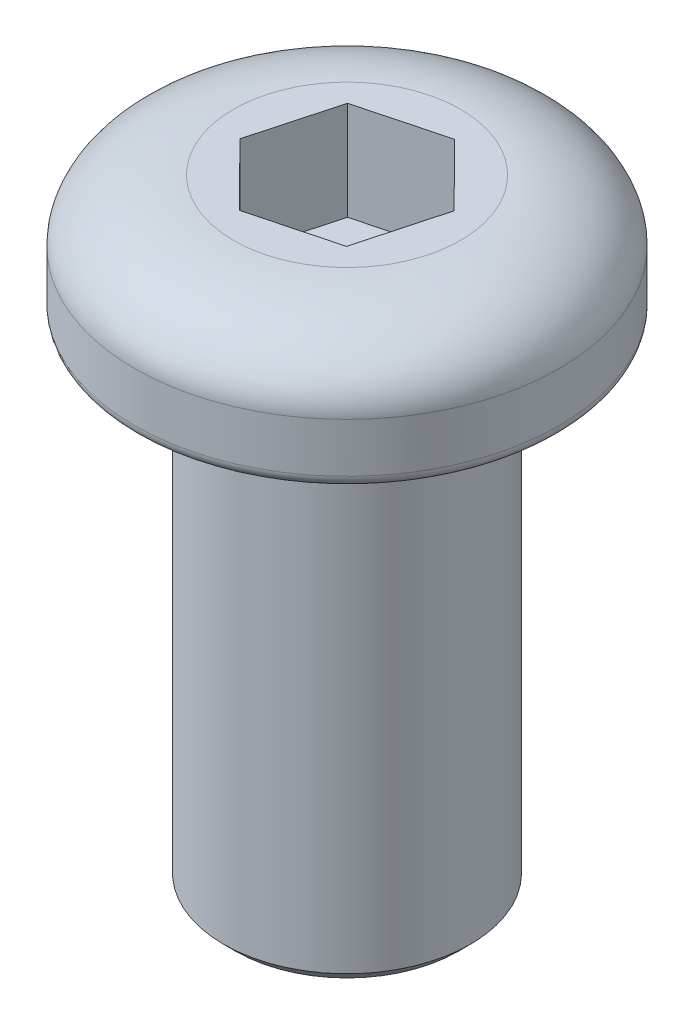
SolidWorks part; units mm, degrees
material "Chrome Stainless Steel"
ref_plane "Front Plane" through (0, 0, 0) normal (0, 0, 1) x (1, 0, 0)
ref_plane "Top Plane" through (0, 0, 0) normal (0, 1, 0) x (1, 0, 0)
ref_plane "Right Plane" through (0, 0, 0) normal (1, 0, 0) x (0, 0, -1)
sketch "Sketch1" plane through (0, 0, 0) normal (0, 1, 0) x (1, 0, 0)
  circle A0 centre (0, 0) radius 5
  dimension "D1" = 10
extrude "Boss-Extrude1" add sketch "Sketch1" along normal blind 20
sketch "Sketch2" plane through (0, 20, 0) normal (0, 1, 0) x (1, 0, 0)
  circle A0 centre (0, 0) radius 8.6
  dimension "D1" = 17.2
extrude "Boss-Extrude2" add sketch "Sketch2" along normal blind 5
fillet "Fillet1" radius 2.5 1 edges at (0, 25, 8.6) second distance 4 first distance on face at (0, 25, 8.6)
sketch "Sketch3" plane through (0, 25, 0) normal (0, 1, 0) x (1, 0, 0)
  line L1 (2.501, -2.5204) -> (3.4332, 0.9057)
  line L2 (3.4332, 0.9057) -> (0.9322, 3.4261)
  line L3 (0.9322, 3.4261) -> (-2.501, 2.5204)
  line L4 (-2.501, 2.5204) -> (-3.4332, -0.9057)
  line L5 (-3.4332, -0.9057) -> (-0.9322, -3.4261)
  line L6 (-0.9322, -3.4261) -> (2.501, -2.5204)
  circle A0 centre (0, 0) radius 3.075 construction
  dimension "D1" = 6.15
extrude "Cut-Extrude1" cut sketch "Sketch3" against normal blind 4
fillet "Fillet2" radius 0.5 1 edges at (0, 20, 8.6)
chamfer "Chamfer1" distance 0.5 angle 45 1 edges at (0, 0, 5)
